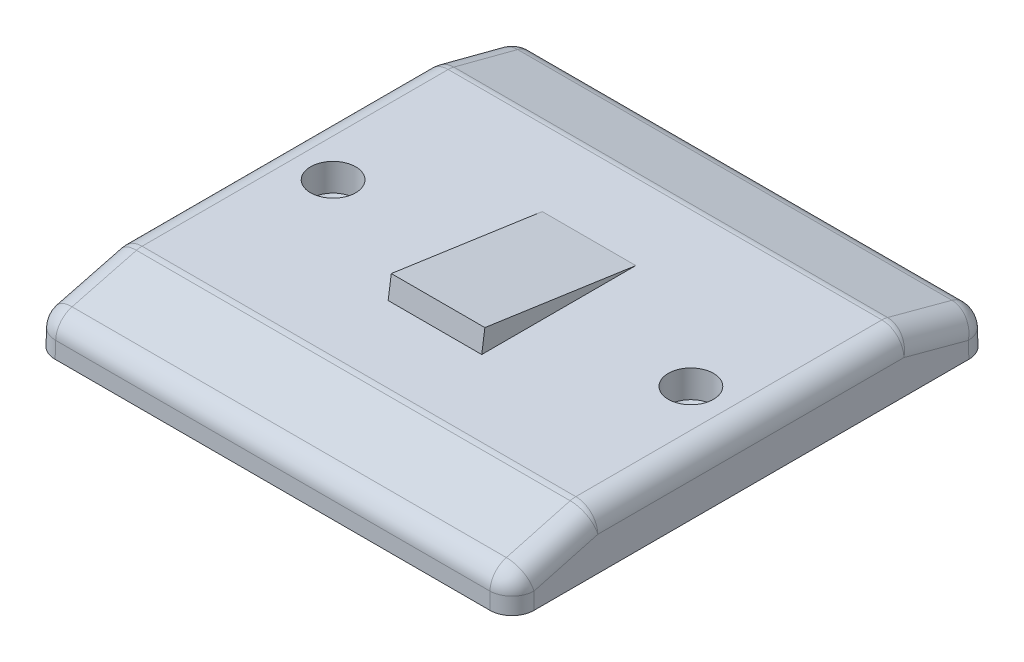
SolidWorks part; units mm, degrees
material "PMMA"
ref_plane "Front Plane" through (0, 0, 0) normal (0, 0, 1) x (1, 0, 0)
ref_plane "Top Plane" through (0, 0, 0) normal (0, 1, 0) x (1, 0, 0)
ref_plane "Right Plane" through (0, 0, 0) normal (1, 0, 0) x (0, 0, -1)
sketch "Sketch1" plane through (0, 0, 0) normal (0, 1, 0) x (1, 0, 0)
  line L1 (-43.5, -43.5) -> (43.5, -43.5)
  line L2 (-43.5, -43.5) -> (-43.5, 43.5)
  line L3 (-43.5, 43.5) -> (43.5, 43.5)
  line L4 (43.5, -43.5) -> (43.5, 43.5)
  line L5 (-43.5, -43.5) -> (43.5, 43.5) construction
  line L6 (-43.5, 43.5) -> (43.5, -43.5) construction
  point P0 (0, 0)
  dimension "D1" = 87
extrude "Boss-Extrude1" add sketch "Sketch1" along normal blind 10 draft 1
chamfer "Chamfer1" distance 4 distance2 15 2 edges at (0, 10, -43.3254) (0, 10, 43.3254)
sketch "Sketch2" plane through (0, 0, 0) normal (1, 0, 0) x (0, 0, -1)
  line L0 (-14, 10) -> (-13.4286, 13.959)
  line L1 (-13.4286, 13.959) -> (14, 10)
  line L2 (14, 10) -> (-14, 10)
  line L3 (-28.3254, 10) -> (28.3254, 10) construction
  point P5 (0, 10)
  dimension "D1" = 4
  dimension "D2" = 28
extrude "Boss-Extrude2" add sketch "Sketch2" along normal mid plane 17
fillet "Fillet1" radius 4 14 edges at (0, 6.0006, -43.3953) (-43.4476, 3.0003, -43.4476) (43.4476, 3.0003, -43.4476) (43.3604, 8.0003, -35.8604) (43.4476, 3.0003, 43.4476) (-43.4476, 3.0003, 43.4476) (-43.3604, 8.0003, 35.8604) (-43.3604, 8.0003, -35.8604) (-43.3254, 10, 0) (0, 10, -28.3254) (43.3254, 10, 0) (43.3604, 8.0003, 35.8604) (0, 6.0006, 43.3953) (0, 10, 28.3254)
hole_wizard "CSK for M3.5 Flat Head Machine Screw1" positions "Sketch5" profile "Sketch3" countersink size "M3.5" standard "ANSI Metric" end condition through all
sketch "Sketch5" plane through (0, 10, 0) normal (0, 1, 0) x (1, 0, 0)
  line L0 (-32.5, 0) -> (32.5, 0) construction
  line L3 (0, 14) -> (0, -14) construction
  line L4 (8.5, 14) -> (-8.5, 14) construction
  line L5 (8.5, -14) -> (-8.5, -14) construction
  point P0 (-32.5, 0)
  point P2 (32.5, 0)
  point P19 (0, 0)
  dimension "D1" = 65
sketch "Sketch3" plane through (-32.5, 10, 0) normal (1, 0, 0) x (0, 0, 1)
  line L0 (0, 0) -> (0, 10)
  line L1 (0, 10) -> (1.95, 10)
  line L2 (1.95, 10) -> (1.95, 7.15)
  line L3 (1.95, 7.15) -> (4.1, 5)
  line L4 (4.1, 5) -> (4.1, 0)
  line L6 (4.1, 0) -> (0, 0)
  line L7 (-1.95, 7.15) -> (-4.1, 5) construction
  line L11 (0, -6.35) -> (0, 107.95) construction
  dimension "Thru Hole Dia." = 3.9
  dimension "Thru Hole Depth" = 10
  dimension "C'Sink Dia." = 8.2
  dimension "C'Sink Angle" = 90
  dimension "Head Clearance" = 5
